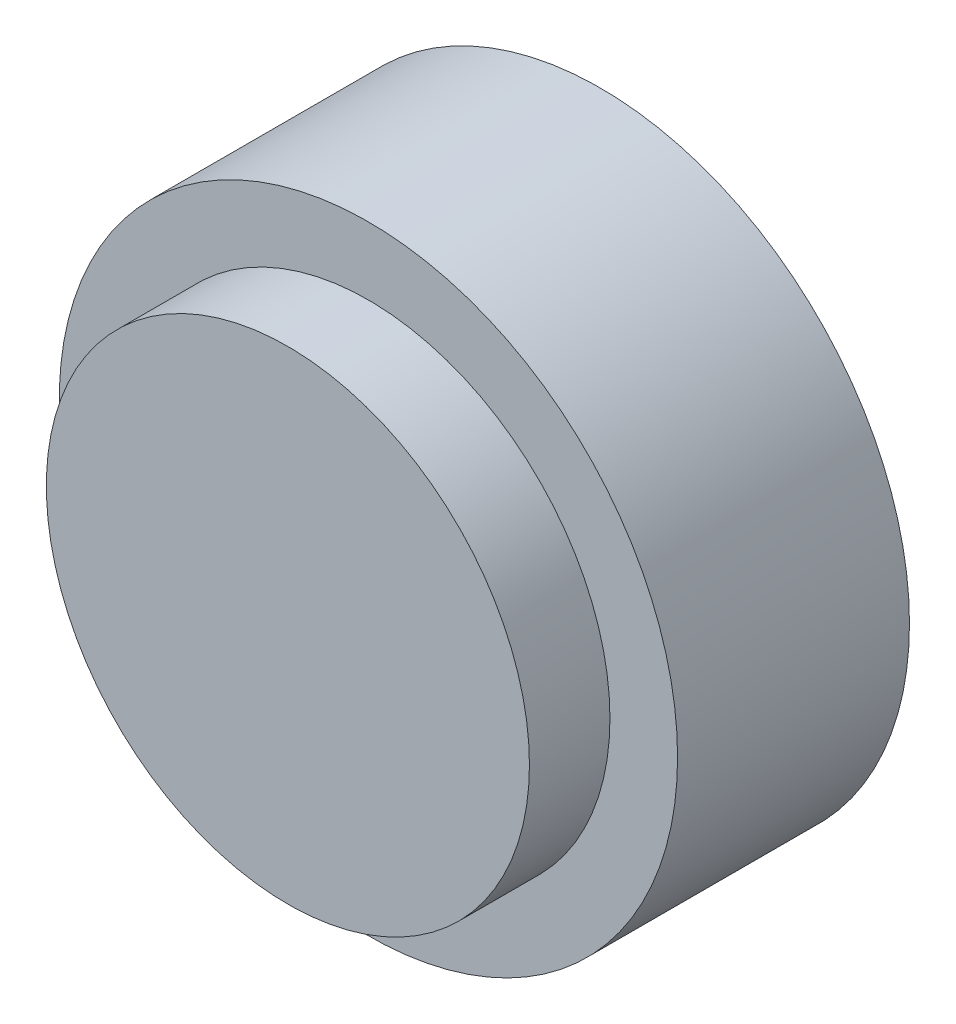
SolidWorks part; units mm, degrees
ref_plane "Front Plane" through (0, 0, 0) normal (0, 0, 1) x (1, 0, 0)
ref_plane "Top Plane" through (0, 0, 0) normal (0, 1, 0) x (1, 0, 0)
ref_plane "Right Plane" through (0, 0, 0) normal (1, 0, 0) x (0, 0, -1)
sketch "Sketch1" plane through (0, 0, 0) normal (0, 0, 1) x (1, 0, 0)
  circle A0 centre (0, 0) radius 48
  circle A1 centre (0, 0) radius 37.5
  circle A2 centre (0, 0) radius 21
  dimension "D1" = 96
  dimension "D2" = 75
  dimension "D3" = 42
extrude "Boss-Extrude1" add sketch "Sketch1" along normal blind 12.5 contours A1 A2 | A2 region at (-36.4393, 0, 0) region at (0, 0, 0)
extrude "Boss-Extrude2" add sketch "Sketch1<3>" against normal blind 36 contours A0 A1 | A1 A2 region at (-46.6424, 0, 0) region at (-36.4393, 0, 0)
sketch "Sketch1<3>" plane through (0, 0, 0) normal (0, 0, 1) x (1, 0, 0) same geometry as "Sketch1"
ref_plane "Plane1" through (0, 0, -36) normal (0, 0, -1) x (-1, 0, 0)
sketch "Sketch2" plane through (0, 0, -36) normal (0, 0, -1) x (-1, 0, 0)
  line L0 (0, 0) -> (0, 52.4537) construction
  circle A0 centre (0, 42) radius 2
  circle A1 centre (29.6985, 29.6985) radius 2
  circle A2 centre (42, 0) radius 2
  circle A3 centre (29.6985, -29.6985) radius 2
  circle A4 centre (0, -42) radius 2
  circle A5 centre (-29.6985, -29.6985) radius 2
  circle A6 centre (-42, 0) radius 2
  circle A7 centre (-29.6985, 29.6985) radius 2
  point P3 (0, 42)
  point P22 (0, 0)
  dimension "D2" = 4
  dimension "D1" = 42
  dimension "D3" = 8
hole_wizard "M4 Tapped Hole1" positions "Sketch3" profile "Sketch4" tap size "M4" standard "ISO"
sketch "Sketch3" plane through (0, 0, -36) normal (0, 0, -1) x (-1, 0, 0)
  point P0 (0, 42)
  point P3 (29.6985, 29.6985)
  point P6 (42, 0)
  point P9 (29.6985, -29.6985)
  point P12 (0, -42)
  point P15 (-29.6985, -29.6985)
  point P18 (-42, 0)
  point P21 (-29.6985, 29.6985)
sketch "Sketch4" plane through (0, 42, -36) normal (1, 0, 0) x (0, 1, 0)
  line L0 (0, 0) -> (0, 8.9914)
  line L1 (0, 8.9914) -> (1.65, 8)
  line L2 (1.65, 8) -> (1.65, 0.375)
  line L3 (1.65, 0.375) -> (2.025, 0)
  line L5 (2.025, 0) -> (0, 0)
  line L6 (-1.65, 0.375) -> (-2.025, 0) construction
  line L10 (0, 8.9914) -> (-1.65, 8) construction
  line L11 (0, -6.35) -> (0, 107.95) construction
  dimension "Tap Drill Dia." = 3.3
  dimension "Tap Drill Depth" = 8
  dimension "Near C'Sink Dia." = 4.05
  dimension "Near C'Sink Angle" = 90
  dimension "Drill Angle" = 118
cosmetic thread "Hole Thread1"
cosmetic thread "Hole Thread2"
cosmetic thread "Hole Thread3"
cosmetic thread "Hole Thread4"
cosmetic thread "Hole Thread5"
cosmetic thread "Hole Thread6"
cosmetic thread "Hole Thread7"
cosmetic thread "Hole Thread8"
